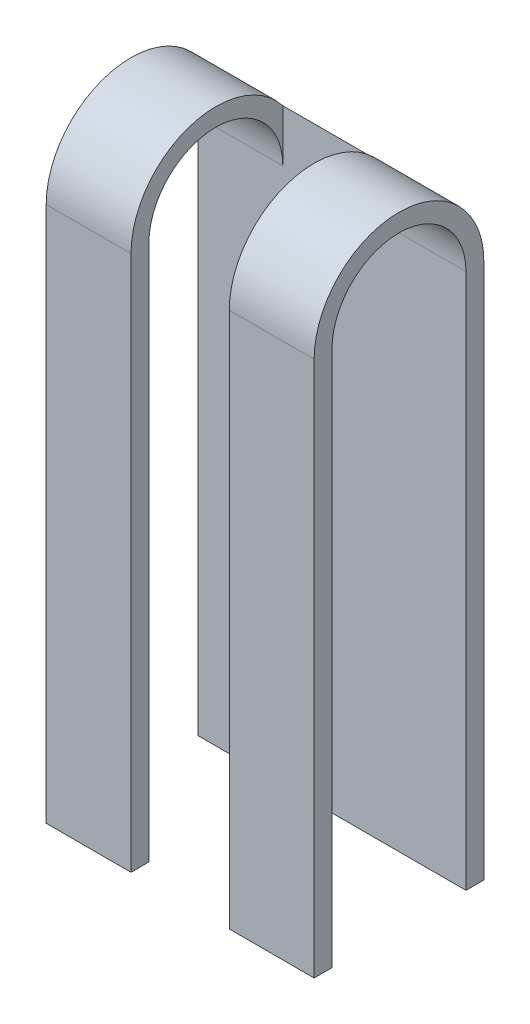
SolidWorks part; units mm, degrees
ref_plane "Front Plane" through (0, 0, 0) normal (0, 0, 1) x (1, 0, 0)
ref_plane "Top Plane" through (0, 0, 0) normal (0, 1, 0) x (1, 0, 0)
ref_plane "Right Plane" through (0, 0, 0) normal (1, 0, 0) x (0, 0, -1)
sketch "Sketch1" plane through (0, 0, 0) normal (1, 0, 0) x (0, 0, -1)
  line L0 (0, 0) -> (0, 60)
  line L1 (0, 60) -> (15, 60)
  line L2 (15, 60) -> (15, 0)
  line L3 (0, 0) -> (-2, 0)
  line L4 (-2, 0) -> (-2, 60)
  line L5 (15, 0) -> (17, 0)
  line L6 (17, 0) -> (17, 60)
  arc A0 (0, 60) -> (15, 60) centre (7.5, 60) cw
  arc A1 (-2, 60) -> (17, 60) centre (7.5, 60) cw
  dimension "D3" = 2
  dimension "D1" = 60
  dimension "D2" = 15
extrude "Boss-Extrude1" add sketch "Sketch1" against normal blind 30 contours A1 L4 L3 L0 A0 L2 L5 L6 region at (0, 0.7205, 1)
sketch "Sketch2" plane through (0, 0, 2) normal (0, 0, 1) x (1, 0, 0)
  line L0 (-15, 69.5) -> (-15, 0) construction
  line L2 (-30, 0) -> (0, 0) construction
  line L3 (0, 69.5) -> (-30, 69.5) construction
  line L4 (-20.5, 69.5) -> (-20.5, 0)
  line L5 (-20.5, 69.5) -> (-9.5, 69.5)
  line L6 (-15, 69.5) -> (-15, 0)
  line L7 (-9.5, 0) -> (-20.5, 0)
  line L8 (-9.5, 69.5) -> (-9.5, 0)
  line M8 (0, 60) -> (-30, 60)
  line M10 (-30, 0) -> (0, 0)
  dimension "D1" = 5.5
extrude "Cut-Extrude1" cut sketch "Sketch2" against normal blind 17 contours L8 L6 M8 M10 | L6 L4 M8 M10 | L6 L5 L4 M8 | L8 L5 L6 M8 region at (-17.75, 64.75, 2) region at (-17.75, 30, 2) region at (-12.25, 64.75, 2) region at (-12.25, 30, 2)
